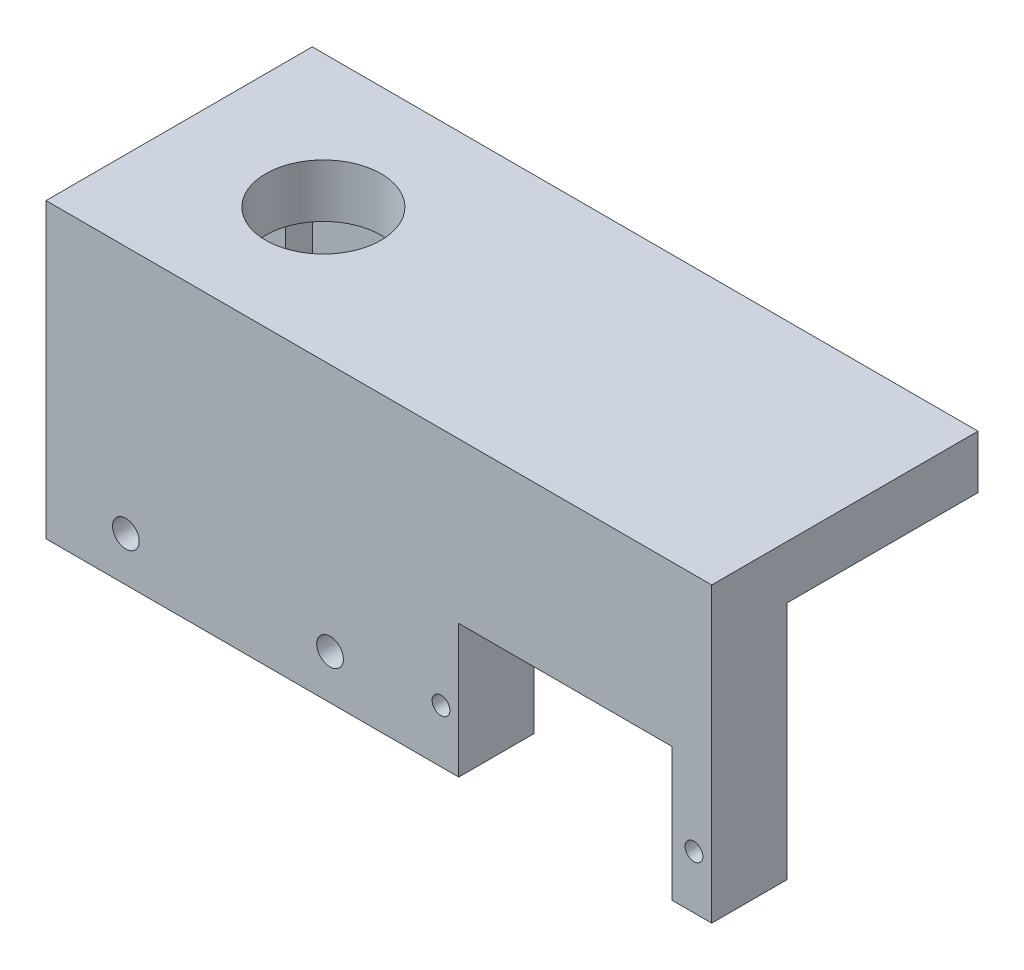
SolidWorks part; units mm, degrees
ref_plane "Front Plane" through (0, 0, 0) normal (0, 0, 1) x (1, 0, 0)
ref_plane "Top Plane" through (0, 0, 0) normal (0, 1, 0) x (1, 0, 0)
ref_plane "Right Plane" through (0, 0, 0) normal (1, 0, 0) x (0, 0, -1)
sketch "Sketch1" plane through (0, -4.342, 0) normal (0, -1, 0) x (1, 0, 0)
  line L0 (-40.9843, 28.2004) -> (-18.4843, 28.2004) construction
  line L1 (-11.5696, 28.2004) -> (-86.5696, 28.2004)
  line L2 (-11.5696, 28.2004) -> (-11.5696, -1.7996)
  line L3 (-11.5696, -1.7996) -> (-86.5696, -1.7996)
  line L4 (-86.5696, 28.2004) -> (-86.5696, -1.7996)
  dimension "D1" = 75
  dimension "D2" = 30
extrude "Boss-Extrude1" add sketch "Sketch1" along normal blind 6 contours L1 L4 L3 L2
sketch "Sketch2" plane through (0, -10.342, 0) normal (0, -1, 0) x (-1, 0, 0)
  line L1 (86.5696, 1.7996) -> (38.5696, 1.7996)
  line L2 (86.5696, 1.7996) -> (86.5696, -2.7004)
  line L3 (86.5696, -2.7004) -> (38.5696, -2.7004)
  line L4 (38.5696, 1.7996) -> (38.5696, -2.7004)
  line L5 (38.5696, 1.7996) -> (43.5696, 1.7996)
  line L6 (38.5696, 1.7996) -> (38.5696, -7.2004)
  line L7 (38.5696, -7.2004) -> (43.5696, -7.2004)
  line L8 (43.5696, 1.7996) -> (43.5696, -7.2004)
  line L9 (11.5696, -28.2004) -> (86.5696, -28.2004) construction
  line L10 (86.5696, 1.7996) -> (82.0696, 1.7996)
  line L11 (86.5696, 1.7996) -> (86.5696, -28.2004)
  line L12 (86.5696, -28.2004) -> (82.0696, -28.2004)
  line L13 (82.0696, 1.7996) -> (82.0696, -28.2004)
  line L14 (11.5696, -28.2004) -> (11.5696, 1.7996) construction
  line L15 (86.5696, -28.2004) -> (40.0696, -28.2004)
  line L16 (86.5696, -28.2004) -> (86.5696, -23.7004)
  line L17 (86.5696, -23.7004) -> (40.0696, -23.7004)
  line L18 (40.0696, -28.2004) -> (40.0696, -23.7004)
  line L19 (46.0696, -28.2004) -> (40.0696, -28.2004)
  line L20 (46.0696, -28.2004) -> (46.0696, -19.7004)
  line L21 (46.0696, -19.7004) -> (40.0696, -19.7004)
  line L22 (40.0696, -28.2004) -> (40.0696, -19.7004)
  line L24 (11.5696, -28.2004) -> (16.0696, -28.2004)
  line L25 (11.5696, -28.2004) -> (11.5696, -19.7004)
  line L26 (11.5696, -19.7004) -> (16.0696, -19.7004)
  line L27 (16.0696, -28.2004) -> (16.0696, -19.7004)
  dimension "D1" = 4.5
  dimension "D2" = 48
  dimension "D3" = 5
  dimension "D4" = 9
  dimension "D5" = 4.5
  dimension "D6" = 4.5
  dimension "D7" = 0
  dimension "D8" = 28.5
  dimension "D9" = 40.5
  dimension "D10" = 8.5
  dimension "D11" = 8.5
  dimension "D12" = 4.5
extrude "Boss-Extrude4" add sketch "Sketch2" along normal blind 27 contours L16 L15 L18 L17 | L2 L1 L4 L3 | L11 L10 L13 L12 | L6 L5 L8 L7 | L20 L19 L22 L21 | L25 L24 L27 L26
sketch "Sketch7" plane through (-38.5696, 0, 0) normal (1, 0, 0) x (0, 0, -1)
  line L1 (-7.2004, -37.342) -> (-2.7004, -37.342)
  line L2 (-7.2004, -37.342) -> (-7.2004, -22.342)
  line L3 (-7.2004, -22.342) -> (-2.7004, -22.342)
  line L4 (-2.7004, -37.342) -> (-2.7004, -22.342)
  dimension "D1" = 15
  dimension "D2" = 4.5
extrude "Cut-Extrude1" cut sketch "Sketch7" against normal blind 6
sketch "Sketch9" plane through (0, -4.342, 0) normal (0, 1, 0) x (1, 0, 0)
  line L1 (-86.5696, -28.2004) -> (-86.5696, 1.7996) construction
  line L2 (-11.5696, 1.7996) -> (-86.5696, 1.7996) construction
  circle A0 centre (-70.3196, -13.2004) radius 6.5
  dimension "D1" = 16.25
  dimension "D2" = 15
  dimension "D3" = 13
extrude "Cut-Extrude2" cut sketch "Sketch9" against normal blind 30
sketch "Sketch10" plane through (0, 0, 28.2004) normal (0, 0, 1) x (1, 0, 0)
  line L0 (-86.5696, -37.342) -> (-86.5696, -4.342) construction
  line L2 (-86.5696, -37.342) -> (-40.0696, -37.342) construction
  circle A0 centre (-77.5696, -32.342) radius 1.5
  dimension "D1" = 9
  dimension "D2" = 3
  dimension "D3" = 5
extrude "Cut-Extrude3" cut sketch "Sketch10" against normal blind 50
sketch "Sketch11" plane through (0, 0, 28.2004) normal (0, 0, 1) x (1, 0, 0)
  line L0 (-86.5696, -37.342) -> (-86.5696, -4.342) construction
  circle A0 centre (-54.5696, -32.342) radius 1.5
  circle A1 centre (-77.5696, -32.342) radius 1.5 construction
  dimension "D1" = 32
  dimension "D2" = 3
  dimension "D3" = 0
extrude "Cut-Extrude4" cut sketch "Sketch11" against normal blind 10
sketch "Sketch12" plane through (-86.5696, 0, 0) normal (-1, 0, 0) x (0, 0, 1)
  line L0 (-1.7996, -37.342) -> (28.2004, -37.342) construction
  line L1 (5.7004, -37.342) -> (20.7004, -37.342)
  line L2 (5.7004, -37.342) -> (5.7004, -11.342)
  line L3 (5.7004, -11.342) -> (20.7004, -11.342)
  line L4 (20.7004, -37.342) -> (20.7004, -11.342)
  line L5 (28.2004, -4.342) -> (-1.7996, -4.342) construction
  point P8 (13.2004, -4.342)
  dimension "D1" = 15
  dimension "D2" = 7.5
  dimension "D3" = 26
extrude "Cut-Extrude5" cut sketch "Sketch12" against normal blind 5
sketch "Sketch14" plane through (-40.0696, 0, 0) normal (1, 0, 0) x (0, 0, -1)
  line L1 (-19.7004, -22.342) -> (-28.2004, -22.342)
  line L2 (-19.7004, -22.342) -> (-19.7004, -10.342)
  line L3 (-19.7004, -10.342) -> (-28.2004, -10.342)
  line L4 (-28.2004, -22.342) -> (-28.2004, -10.342)
  dimension "D1" = 12
extrude "Boss-Extrude6" add sketch "Sketch14" along normal up to vertex (24 mm away) up to point (-16.0696, -10.342, 28.2004)
sketch "Sketch15" plane through (0, 0, 28.2004) normal (0, 0, 1) x (1, 0, 0)
  line L0 (-11.5696, -37.342) -> (-16.0696, -37.342) construction
  line L1 (-11.5696, -37.342) -> (-11.5696, -4.342) construction
  line L2 (-40.0696, -37.342) -> (-40.0696, -22.342) construction
  circle A0 centre (-13.5696, -31.342) radius 1
  circle A1 centre (-42.0696, -31.342) radius 1
  dimension "D1" = 2
  dimension "D2" = 6
  dimension "D3" = 2
  dimension "D4" = 0
  dimension "D5" = 2
  dimension "D6" = 2
extrude "Cut-Extrude6" cut sketch "Sketch15" against normal blind 11
